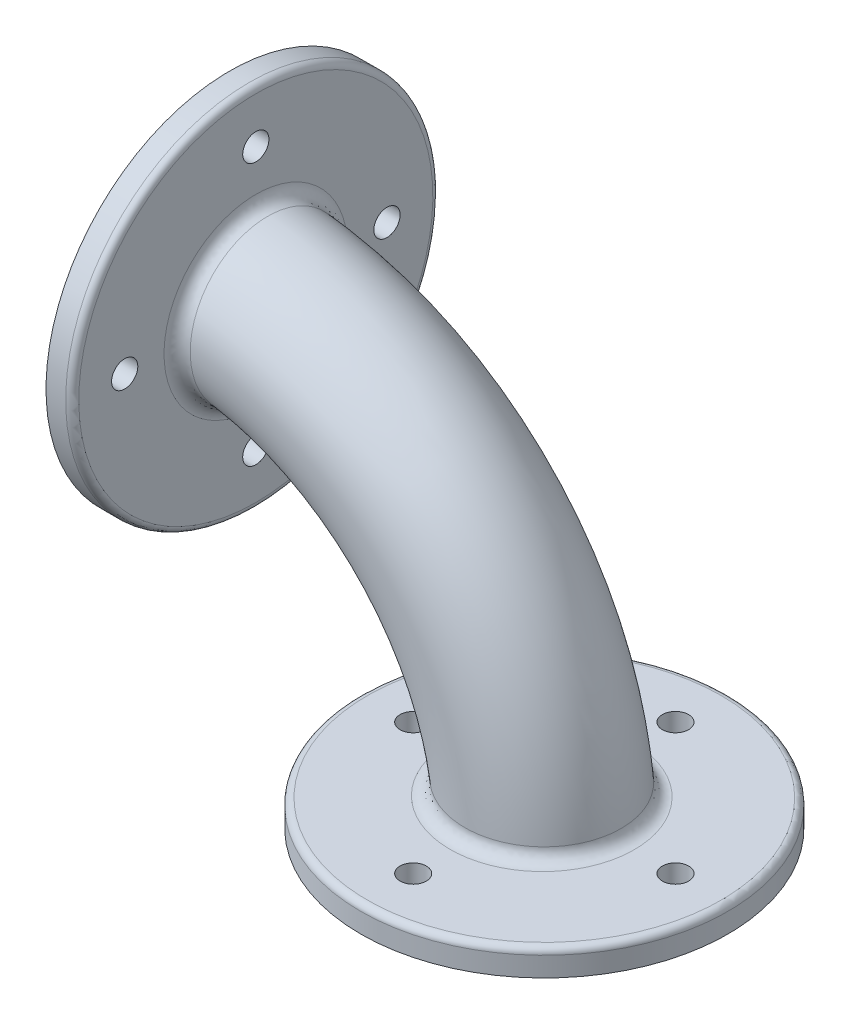
SolidWorks part; units mm, degrees
ref_plane "Front Plane" through (0, 0, 0) normal (0, 0, 1) x (1, 0, 0)
ref_plane "Top Plane" through (0, 0, 0) normal (0, 1, 0) x (1, 0, 0)
ref_plane "Right Plane" through (0, 0, 0) normal (1, 0, 0) x (0, 0, -1)
sketch "Sketch1" plane through (0, 0, 0) normal (0, 0, 1) x (1, 0, 0)
  arc A0 (0, 76.2) -> (76.2, 0) centre (0, 0) cw
  dimension "D1" = 76.2
sketch "Sketch2" plane through (0, 0, 0) normal (0, 1, 0) x (1, 0, 0)
  line L0 (0, 0) -> (76.2, 0) construction
  circle A0 centre (76.2, 0) radius 12.7
  circle A1 centre (76.2, 0) radius 19.05
  dimension "D1" = 25.4
  dimension "D2" = 38.1
  dimension "D3" = 76.2
sweep "Sweep1" add profiles "Sketch2" path "Sketch1"
sketch "Sketch3" plane through (0, 0, 0) normal (0, -1, 0) x (1, 0, 0)
  circle A0 centre (76.2, 0) radius 12.7
  circle A1 centre (76.2, 0) radius 31.75
  circle A2 centre (76.2, 0) radius 44.45
  circle A3 centre (107.95, 0) radius 3.175
  circle A4 centre (76.2, 31.75) radius 3.175
  circle A5 centre (44.45, 0) radius 3.175
  circle A6 centre (76.2, -31.75) radius 3.175
  circle M4 centre (76.2, 0) radius 12.7
  circle M5 centre (76.2, 0) radius 19.05
  dimension "D1" = 6.35
  dimension "D2" = 88.9
  dimension "D3" = 63.5
  dimension "D4" = 25.4
extrude "Boss-Extrude1" add sketch "Sketch3" against normal blind 6.35 contours A2 A6 A1 A5 A4 A3 | A6 A1 A3 A4 A5 M5 | M5 M4 region at (103.8815, 0, 0) region at (33.0072, 0, 0) region at (57.6888, 0, 0)
ref_axis "Axis1" through (0, 0, -48.895) along (0, 0, 1)
ref_plane "Plane1" through (0, 0, 0) normal (-0.7071, 0.7071, 0) x (0, 0, 1)
mirror "Mirror1" about plane through (0, 0, 0) normal (-0.7071, 0.7071, 0) of "Boss-Extrude1"
fillet "Fillet1" radius 3.175 2 edges at (90.8745, 6.35, 11.8747) (6.35, 94.6208, 3.961)
fillet "Fillet2" radius 1.5875 2 edges at (76.2, 6.35, -44.45) (6.35, 76.2, -44.45)
